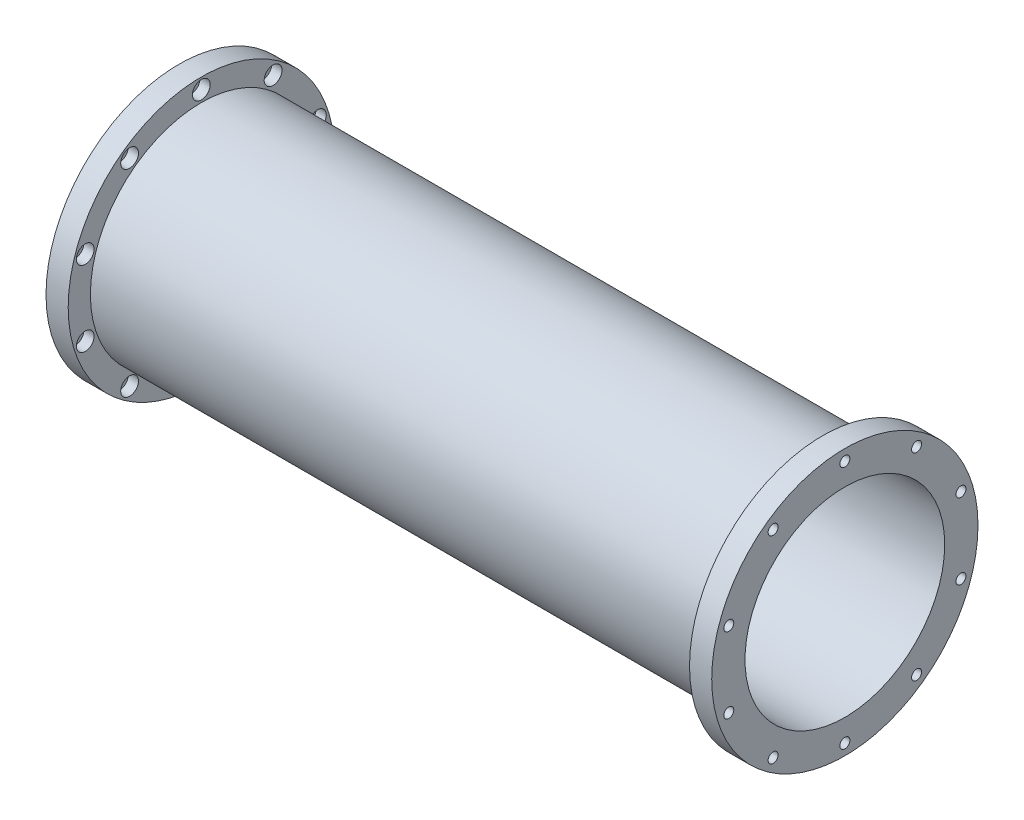
SolidWorks part; units mm, degrees
ref_plane "前视基准面" through (0, 0, 0) normal (0, 0, 1) x (1, 0, 0)
ref_plane "上视基准面" through (0, 0, 0) normal (0, 1, 0) x (1, 0, 0)
ref_plane "右视基准面" through (0, 0, 0) normal (1, 0, 0) x (0, 0, -1)
sketch "草图1" plane through (0, 0, 0) normal (0, 0, 1) x (1, 0, 0)
  line L0 (-244.0828, 0) -> (270.7101, 0) construction
  line L1 (0, 0) -> (0, 109.3935) construction
  line L2 (140, 50) -> (-140, 50)
  line L3 (-140, 60) -> (-140, 50)
  line L4 (-140, 60) -> (-150, 60)
  line L5 (-150, 60) -> (-150, 0)
  line L6 (-150, 0) -> (150, 0)
  line L9 (150, 60) -> (150, 0)
  line L10 (140, 60) -> (150, 60)
  line L11 (140, 60) -> (140, 50)
  point P16 (0, 50)
  dimension "D1" = 300
  dimension "D2" = 10
  dimension "D3" = 50
  dimension "D4" = 60
revolve "旋转1" add sketch "草图1" angle 360 about L6
sketch "草图3" plane through (150, 0, 0) normal (1, 0, 0) x (0, 0, -1)
  circle A0 centre (0, 0) radius 45
  dimension "D1" = 90
extrude "切除-拉伸1" cut sketch "草图3" against normal through all contours A0
hole_wizard "打孔尺寸(%根据)内六角圆柱头螺钉的类型4" positions "草图20" profile "草图19" counterbore size "M4" standard "GB" end condition through all
sketch "草图20" plane through (-140, 0, 0) normal (1, 0, 0) x (0, 0, -1)
  line L0 (0, 0) -> (0, 71.0561) construction
  circle A0 centre (0, 0) radius 55 construction
  point P0 (0, 55)
  dimension "D1" = 110
sketch "草图19" plane through (-140, 55, 0) normal (0, 1, 0) x (0, 0, -1)
  line L0 (0, 0) -> (0, 10)
  line L1 (0, 10) -> (2.25, 10)
  line L3 (2.25, 10) -> (2.25, 4.6)
  line L4 (2.25, 4.6) -> (4, 4.6)
  line L5 (4, 4.6) -> (4, 0)
  line L7 (4, 0) -> (0, 0)
  line L11 (0, -6.35) -> (0, 107.95) construction
  dimension "通孔孔直径" = 4.5
  dimension "通孔孔深度" = 10
  dimension "柱形沉头孔直径" = 8
  dimension "柱形沉头孔深度" = 4.6
ref_axis "基准轴1" through (-150, 0, 0) along (1, 0, 0)
pattern_circular "阵列(圆周)1" count 10 over 360 about axis through (-150, 0, 0) along (1, 0, 0) of "打孔尺寸(%根据)内六角圆柱头螺钉的类型4"
mirror "镜向1" about plane through (0, 0, 0) normal (1, 0, 0) of "阵列(圆周)1"
